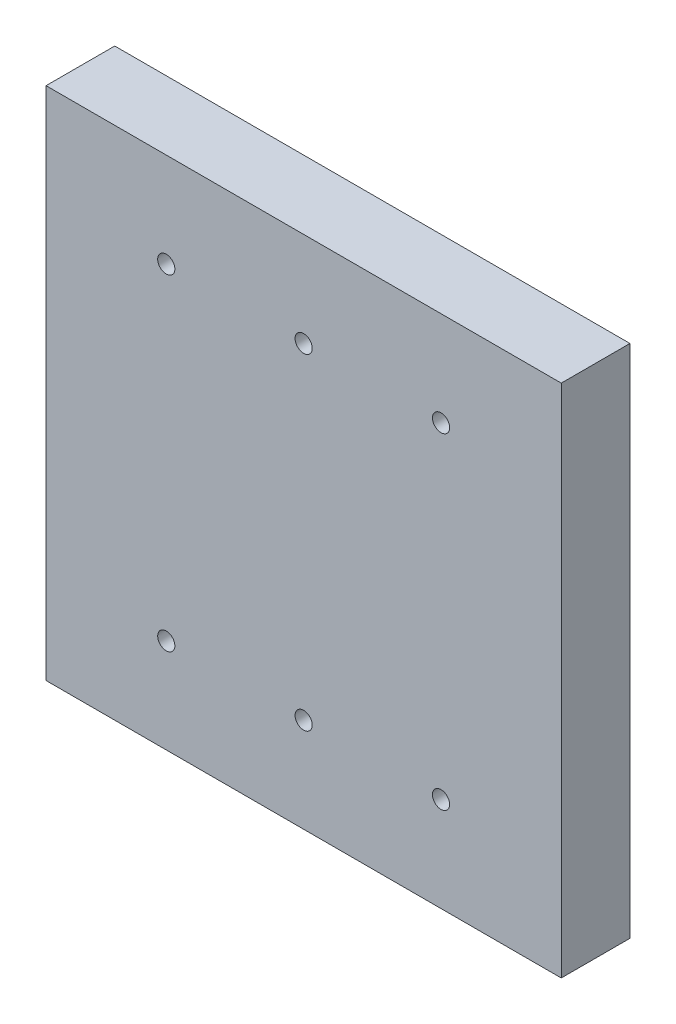
SolidWorks part; units mm, degrees
material "AISI 1020 Steel, Cold Rolled"
ref_plane "Front Plane" through (0, 0, 0) normal (0, 0, 1) x (1, 0, 0)
ref_plane "Top Plane" through (0, 0, 0) normal (0, 1, 0) x (1, 0, 0)
ref_plane "Right Plane" through (0, 0, 0) normal (1, 0, 0) x (0, 0, -1)
sketch "Sketch1" plane through (0, 0, 0) normal (0, 0, 1) x (1, 0, 0)
  line L0 (-150, 150) -> (-120, 150)
  line L1 (-150, -150) -> (150, -150)
  line L2 (-150, -150) -> (-150, 150)
  line L3 (-150, 150) -> (150, 150)
  line L4 (150, -150) -> (150, 150)
  line L5 (-150, -150) -> (150, 150) construction
  line L6 (-150, 150) -> (150, -150) construction
  line L7 (120, -120) -> (0, -120)
  line L8 (-55.8039, 120) -> (-120, 120)
  line L9 (-120, -120) -> (-120, 120)
  line L10 (120, 120) -> (-55.8039, 120)
  line L11 (0, -120) -> (-120, -120)
  line L12 (0, -120) -> (0, -95)
  line L13 (0, -95) -> (-80, -95)
  line L14 (120, 0) -> (120, 120)
  line L15 (120, 0) -> (120, -120)
  line L16 (0, -95) -> (80, -95)
  line L17 (0, 120) -> (0, 95)
  line L18 (0, 95) -> (-80, 95)
  line L19 (0, 95) -> (80, 95)
  circle A0 centre (-80, -95) radius 5
  circle A1 centre (0, -95) radius 5
  circle A2 centre (80, -95) radius 5
  circle A3 centre (0, 95) radius 5
  circle A4 centre (-80, 95) radius 5
  circle A5 centre (80, 95) radius 5
  point P0 (0, 0)
  dimension "D1" = 300
  dimension "D2" = 300
  dimension "D3" = 240
  dimension "D4" = 240
  dimension "D5" = 30
  dimension "D6" = 30
  dimension "D7" = 30
extrude "Boss-Extrude1" add sketch "Sketch1" along normal blind 10 contours L4 L3 L2 L1
ref_plane "Plane7" through (-150, -150, 10) normal (0, 0, -1) x (-1, 0, 0)
extrude "Boss-Extrude4" add sketch "Sketch1<6>" against normal blind 30 contours L1 L4 L3 L0 L2 L14 L15 L7 L11 L9 L8 L10 region at (-135, 145.7574, 0)
sketch "Sketch1<6>" plane through (0, 0, 0) normal (0, 0, 1) x (1, 0, 0) same geometry as "Sketch1"
extrude "Cut-Extrude2" cut sketch "Sketch1<11>" against normal through all and the other way through all contours A2 | A5 | L18 A3 L19 | L19 A3 L17 | L17 A3 L18 | A4 | L16 A1 L13 | L13 A1 L12 | L12 A1 L16 | A0 | A0 | A1 region at (80, 99.8586, 0) region at (-84.8586, 95, 0) region at (2.1221, 97.1221, 0) region at (-2.1221, 97.1221, 0) region at (-84.8586, -95, 0) region at (80, -90.1414, 0) region at (-2.1221, -97.1221, 0) region at (2.1221, -97.1221, 0) region at (0, -92.8779, 0) region at (0, 92.8779, 0)
sketch "Sketch1<11>" plane through (0, 0, 0) normal (0, 0, 1) x (1, 0, 0) same geometry as "Sketch1"
